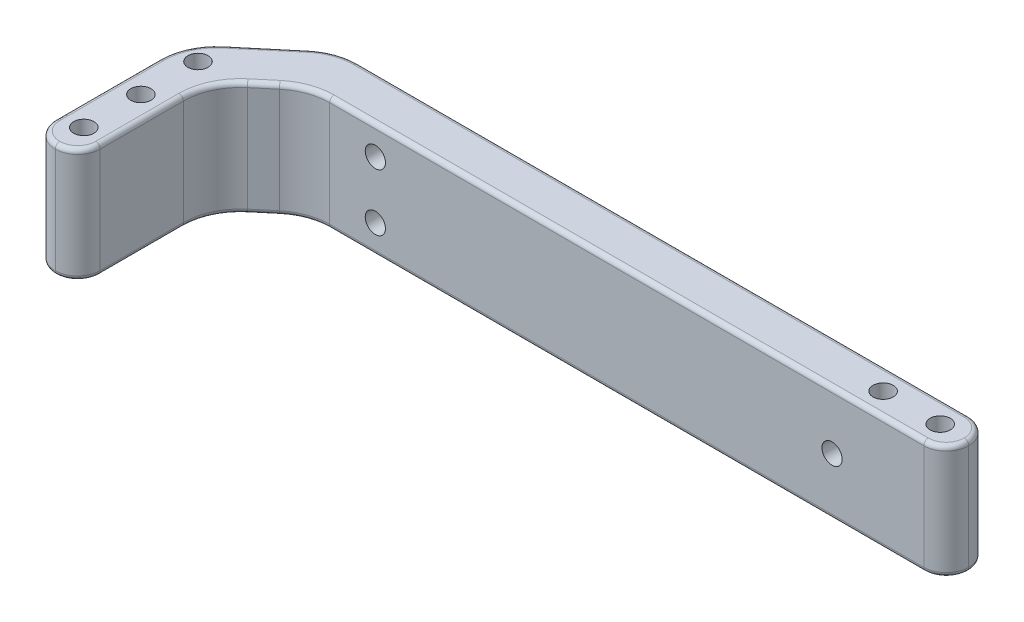
SolidWorks part; units mm, degrees
ref_plane "Front Plane" through (0, 0, 0) normal (0, 0, 1) x (1, 0, 0)
ref_plane "Top Plane" through (0, 0, 0) normal (0, 1, 0) x (1, 0, 0)
ref_plane "Right Plane" through (0, 0, 0) normal (1, 0, 0) x (0, 0, -1)
sketch "Sketch1" plane through (0, 0, 0) normal (0, 1, 0) x (1, 0, 0)
  line L0 (0, 0) -> (0, 38.1) construction
  line L1 (0, 38.1) -> (152.4, 38.1) construction
  line L2 (158.75, 43.1) -> (158.75, 33.1)
  line L3 (158.75, 33.1) -> (5, 33.1)
  line L4 (5, 33.1) -> (5, -6.35)
  line L5 (5, -6.35) -> (-5, -6.35)
  line L6 (-5, -6.35) -> (-5, 43.1)
  line L9 (-5, 43.1) -> (158.75, 43.1)
  line L10 (5, 23.0685) -> (16.9551, 33.1)
  line L11 (-5, 27.7315) -> (13.3154, 43.1)
  line L12 (-5, 27.7315) -> (5, 23.0685) construction
  circle A1 centre (152.4, 38.1) radius 2.25
  circle A2 centre (139.7, 38.1) radius 2.25
  circle A3 centre (0, 25.4) radius 2.25
  circle A4 centre (0, 12.7) radius 2.25
  circle A5 centre (0, 0) radius 2.25
  dimension "D3" = 4.5
  dimension "D11" = 5
  dimension "D15" = 5
  dimension "D1" = 38.1
  dimension "D2" = 152.4
  dimension "D4" = 12.7
  dimension "D6" = 10
  dimension "D7" = 10
  dimension "D8" = 50
  dimension "D9" = 6.35
  dimension "D10" = 6.35
  dimension "D5" = 10
  dimension "D12" = 12.7
  dimension "D13" = 12.7
  dimension "D14" = 5
extrude "Boss-Extrude1" add sketch "Sketch1" along normal blind 25.4 contours L11 L6 L5 L4 L3 L2 L9 A5 A4 A3 A2 A1 | L4 L10 L3
fillet "Fillet2" radius 5 4 edges at (-5, 12.7, 6.35) (5, 12.7, 6.35) (158.75, 12.7, -43.1) (158.75, 12.7, -33.1)
sketch "Sketch3" plane through (0, 0, -43.1) normal (0, 0, -1) x (-1, 0, 0)
  line L0 (-158.75, 25.4) -> (-158.75, 0) construction
  line L1 (-13.3154, 25.4) -> (-153.75, 25.4) construction
  circle A0 centre (-31.75, 6.35) radius 2.25
  circle A1 centre (-31.75, 19.05) radius 2.25
  circle A2 centre (-133.35, 12.7) radius 2.25
  dimension "D4" = 4.5
  dimension "D7" = 4.5
  dimension "D1" = 31.75
  dimension "D2" = 12.7
  dimension "D3" = 6.35
  dimension "D5" = 25.4
  dimension "D6" = 12.7
extrude "Cut-Extrude2" cut sketch "Sketch3" against normal up to next
fillet "Fillet4" radius 12.7 4 edges at (16.9551, 12.7, -33.1) (5, 12.7, -23.0685) (13.3154, 12.7, -43.1) (-5, 12.7, -27.7315)
fillet "Fillet5" radius 1 28 edges at (157.2855, 25.4, -34.5645) (157.2855, 25.4, -41.6355) (157.2855, 0, -41.6355) (157.2855, 0, -34.5645) (85.8439, 25.4, -43.1) (85.8439, 0, -43.1) (13.5942, 25.4, -42.3341) (13.5942, 0, -42.3341) (4.6555, 25.4, -35.8335) (4.6555, 0, -35.8335) (-3.8101, 25.4, -27.1767) (-3.8101, 0, -27.1767) (-5, 25.4, -10.2297) (-5, 0, -10.2297) (-3.5355, 25.4, 4.8855) (-3.5355, 0, 4.8855) (3.5355, 25.4, 4.8855) (3.5355, 0, 4.8855) (5, 25.4, -7.8982) (5, 0, -7.8982) (6.1899, 25.4, -22.5136) (6.1899, 0, -22.5136) (11.4754, 25.4, -28.5019) (11.4754, 0, -28.5019) (17.2339, 25.4, -32.3341) (87.6638, 25.4, -33.1) (87.6638, 0, -33.1) (17.2339, 0, -32.3341)
